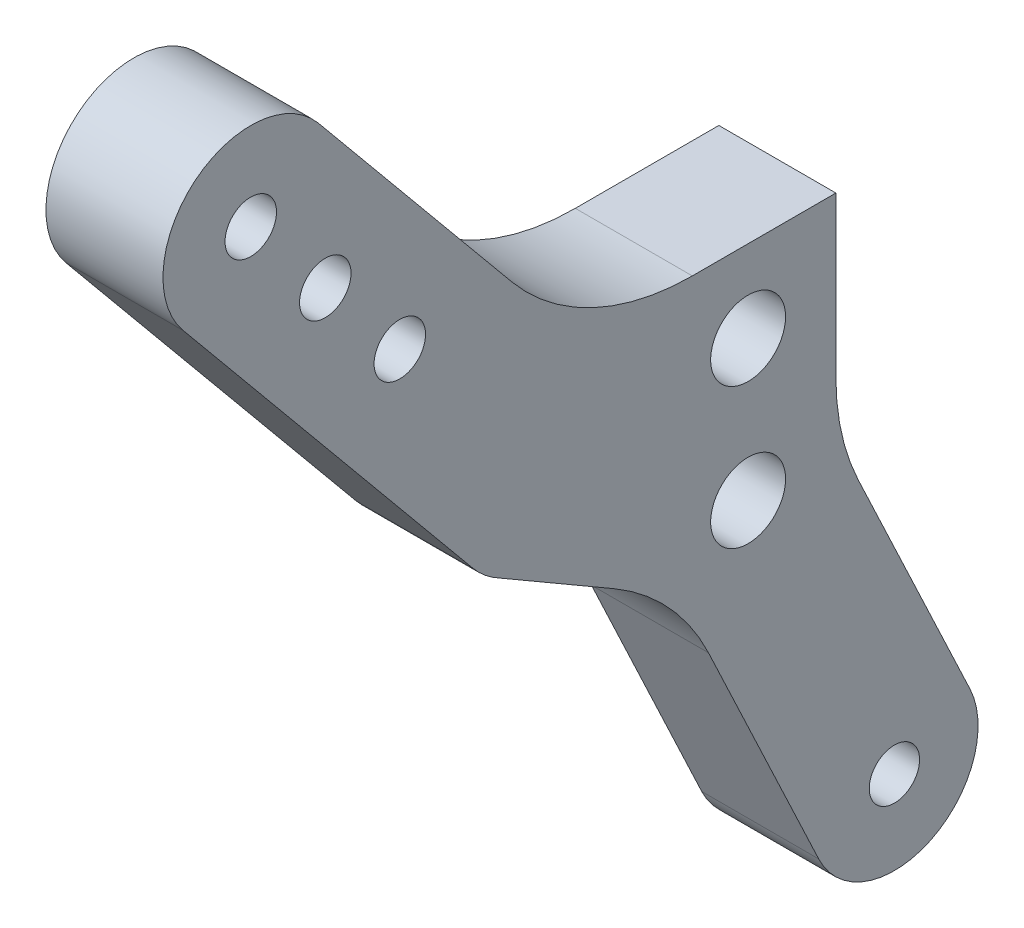
SolidWorks part; units mm, degrees
ref_plane "Front Plane" through (0, 0, 0) normal (0, 0, 1) x (1, 0, 0)
ref_plane "Top Plane" through (0, 0, 0) normal (0, 1, 0) x (1, 0, 0)
ref_plane "Right Plane" through (0, 0, 0) normal (1, 0, 0) x (0, 0, -1)
sketch "Sketch1" plane through (0, 0, 0) normal (0, 0, 1) x (1, 0, 0)
  line L1 (-2.5, -3.75) -> (2.5, -3.75)
  line L2 (-2.5, -3.75) -> (-2.5, 3.75)
  line L3 (-2.5, 3.75) -> (2.5, 3.75)
  line L4 (2.5, -3.75) -> (2.5, 3.75)
  line L5 (-2.5, -3.75) -> (2.5, 3.75) construction
  line L6 (-2.5, 3.75) -> (2.5, -3.75) construction
  point P0 (0, 0)
  dimension "D1" = 5
  dimension "D2" = 7.5
extrude "Boss-Extrude1" add sketch "Sketch1" along normal blind 13
sketch "Sketch6" plane through (2.5, 0, 0) normal (1, 0, 0) x (0, 0, -1)
  line L0 (-12.6104, 0) -> (-25, 15) construction
  line L1 (-15.5017, -2.3881) -> (-27.8913, 12.6119)
  line L2 (-9.7192, 2.3881) -> (-22.1087, 17.3881)
  line L3 (0, 0) -> (-13, 0) construction
  line L4 (0, -3.75) -> (0, 3.75) construction
  line L5 (-13, -3.75) -> (-13, 3.75) construction
  arc A0 (-15.5017, -2.3881) -> (-9.7192, 2.3881) centre (-12.6104, 0) ccw
  arc A1 (-22.1087, 17.3881) -> (-27.8913, 12.6119) centre (-25, 15) ccw
  point P3 (-18.8052, 7.5)
  dimension "D1" = 15
  dimension "D2" = 12
  dimension "D3" = 7.5
extrude "Boss-Extrude4" add sketch "Sketch6" against normal up to surface (5 mm away) contours L1 A1 L2 A0 up to face at (-2.5, 0, 6.5)
sketch "Sketch2" plane through (2.5, 0, 0) normal (1, 0, 0) x (0, 0, -1)
  circle A0 centre (-25, 15) radius 1.1
  arc A1 (-22.1087, 17.3881) -> (-27.8913, 12.6119) centre (-25, 15) ccw construction
  dimension "D1" = 2.2
extrude "Cut-Extrude1" cut sketch "Sketch2" against normal through all
fillet "Fillet1" [suppressed] radius 3.75
pattern_linear "LPattern1" count 3 spacing 5 along (0, -0.771, -0.6368) of "Cut-Extrude1"
sketch "Sketch3" plane through (2.5, 0, 0) normal (1, 0, 0) x (0, 0, -1)
  line L0 (-10.8441, 3.75) -> (0, 3.75) construction
  line L2 (0, -8.75) -> (-7.5, -8.75) construction
  circle A0 centre (-3.75, 0.25) radius 1.6
  point P8 (-3.75, -8.75)
  dimension "D1" = 3.2
  dimension "D2" = 3.5
extrude "Cut-Extrude2" cut sketch "Sketch3" against normal through all
sketch "Sketch4" plane through (2.5, 0, 0) normal (1, 0, 0) x (0, 0, -1)
  line L0 (0, -3.75) -> (0, -8.75)
  line L1 (0, -8.75) -> (-5, -8.75)
  line L2 (-5, -8.75) -> (-14.3827, -3.3048)
  line L4 (-14.3827, -3.3048) -> (0, -3.75)
  arc A0 (-15.5017, -2.3881) -> (-13, -3.7297) centre (-12.6104, 0) ccw construction
  dimension "D2" = 5
  dimension "D3" = 5
extrude "Boss-Extrude2" add sketch "Sketch4" against normal up to surface (5 mm away) contours L0 L1 L2 L4 up to face at (-2.5, 0.25, 2.15)
pattern_linear "LPattern2" count 2 spacing 6 along (0, -1, 0) of "Cut-Extrude2"
sketch "Sketch5" plane through (2.5, 0, 0) normal (1, 0, 0) x (0, 0, -1)
  line L0 (-40.5, -19) -> (2.5, -19) construction
  line L1 (2.5, -44) -> (2.5, -19) construction
  line L2 (2.5, -19) -> (-3.75, -5.75) construction
  line L3 (-0.7333, -20.5252) -> (-6.9833, -7.2752)
  line L4 (5.7333, -17.4748) -> (-0.5167, -4.2248)
  arc A0 (-0.7333, -20.5252) -> (5.7333, -17.4748) centre (2.5, -19) ccw
  arc A1 (-0.5167, -4.2248) -> (-6.9833, -7.2752) centre (-3.75, -5.75) ccw
  circle A2 centre (2.5, -19) radius 1.075
  circle A3 centre (-3.75, -5.75) radius 1.6 construction
  circle A4 centre (-3.75, -5.75) radius 1.6
  circle A5 centre (-40.5, -19) radius 1.1 construction
  point P1 (-0.625, -12.375)
  dimension "D1" = 2.15
  dimension "D2" = 2.5
extrude "Boss-Extrude3" add sketch "Sketch5" against normal up to surface (5 mm away) up to face at (-2.5, -5.75, 2.15)
fillet "Fillet2" radius 10 3 edges at (0, -7.721, 6.773) (0, -5.3202, 0) (0, 3.75, 10.8441)
